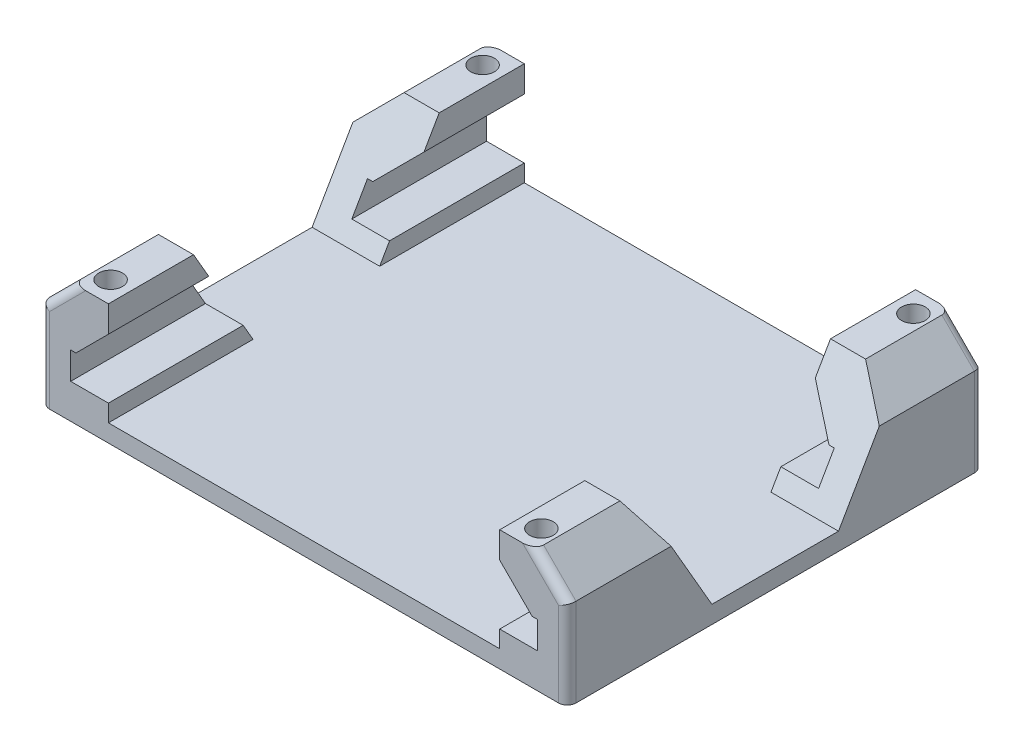
SolidWorks part; units mm, degrees
material "Delrin 2700 NC010, Low Viscosity Acetal Copolymer (SS)"
ref_plane "Front Plane" through (0, 0, 0) normal (0, 0, 1) x (1, 0, 0)
ref_plane "Top Plane" through (0, 0, 0) normal (0, 1, 0) x (1, 0, 0)
ref_plane "Right Plane" through (0, 0, 0) normal (1, 0, 0) x (0, 0, -1)
sketch "Sketch1" plane through (0, 0, 0) normal (0, 0, 1) x (1, 0, 0)
  line L0 (0, 0) -> (30, 0)
  line L1 (30, 0) -> (30, 12.7499)
  line L2 (30, 12.7499) -> (22.3001, 12.7499)
  line L3 (22.3001, 12.7499) -> (22.3001, 9.7499)
  line L4 (22.3001, 9.7499) -> (26, 6.05)
  line L5 (26, 6.05) -> (26, 4.95)
  line L6 (22.3, 1) -> (0, 1)
  line L7 (0, 1) -> (0, 0)
  line L8 (0, 0) -> (0, 12.0857) construction
  line L9 (26, 4.95) -> (22.3, 4.95)
  line L10 (22.3, 4.95) -> (22.3, 1)
  dimension "D1" = 1
  dimension "D2" = 4
  dimension "D3" = 45
  dimension "D5" = 3.95
  dimension "D6" = 1.1
  dimension "D7" = 3.7
  dimension "D8" = 3
  dimension "D9" = 0.0001
  dimension "D10" = 44.6
extrude "Boss-Extrude1" add sketch "Sketch1" against normal blind 46.4
mirror "Mirror1" about plane through (0, 1, -46.4) normal (-1, 0, 0) of bodies 101
sketch "Sketch2" plane through (0, 12.7499, 0) normal (0, 1, 0) x (1, 0, 0)
  circle A1 centre (-24.55, 2) radius 1.35 construction
  circle A2 centre (-24.55, 2) radius 1.35
  circle A13 centre (-24.55, 44.4) radius 1.35 construction
  circle A14 centre (-24.55, 44.4) radius 1.35
  circle A15 centre (24.55, 2) radius 1.35 construction
  circle A16 centre (24.55, 44.4) radius 1.35 construction
  circle A17 centre (24.55, 2) radius 1.35
  circle A18 centre (24.55, 44.4) radius 1.35
extrude "Cut-Extrude1" cut sketch "Sketch2" against normal through all
sketch "Sketch3" plane through (0, 0, 0) normal (0, 0, 1) x (1, 0, 0)
  line L0 (26.3, 12.7499) -> (30, 9.0499)
  line L1 (30, 12.7499) -> (22.3001, 12.7499) construction
  line L2 (30, 0) -> (30, 12.7499) construction
  line L3 (30, 9.0499) -> (30, 12.7499)
  line L4 (30, 12.7499) -> (26.3, 12.7499)
  line L5 (22.3001, 9.7499) -> (26, 6.05) construction
  line L7 (-30, 12.7499) -> (-30, 9.0499)
  line L8 (-30, 0) -> (-30, 12.7499) construction
  line L9 (-30, 9.0499) -> (-26.3, 12.7499)
  line L10 (-30, 12.7499) -> (-22.3001, 12.7499) construction
  line L11 (-26.3, 12.7499) -> (-30, 12.7499)
  line L12 (-22.3001, 9.7499) -> (-26, 6.05) construction
  dimension "D1" = 3.7
extrude "Cut-Extrude2" cut sketch "Sketch3" against normal through all
sketch "Sketch4" plane through (30, 0, 0) normal (1, 0, 0) x (0, 0, -1)
  line L0 (9.2, 12.7499) -> (37.2, 12.7499)
  line L1 (46.4, 12.7499) -> (0, 12.7499) construction
  line L2 (37.2, 12.7499) -> (30.4162, 1)
  line L3 (30.4162, 1) -> (15.9838, 1)
  line L4 (15.9838, 1) -> (9.2, 12.7499)
  line L5 (46.4, 1) -> (0, 1) construction
  point P9 (23.2, 12.7499)
  dimension "D1" = 28
  dimension "D2" = 60
extrude "Cut-Extrude3" cut sketch "Sketch4" against normal through all
other "Move Face1" face at (0, 6.8055, -46.4) face at (0, 6.8055, 0) offset 0.5 parameters "D1"=0.5
sketch "Sketch6" plane through (-26, 0, 0) normal (1, 0, 0) x (0, 0, -1)
  line L4 (13.7033, 4.95) -> (13.0682, 6.05)
  line L5 (13.0682, 6.05) -> (-0.5, 6.05)
  line L6 (-0.5, 6.05) -> (-0.5, 4.95)
  line L7 (-0.5, 4.95) -> (13.7033, 4.95)
  line L8 (13.7033, 4.95) -> (13.0682, 6.05)
  line L9 (13.0682, 6.05) -> (-0.5, 6.05)
  line L10 (-0.5, 6.05) -> (-0.5, 4.95)
  line L11 (-0.5, 4.95) -> (13.7033, 4.95)
  line L12 (33.3318, 6.05) -> (32.6967, 4.95)
  line L13 (32.6967, 4.95) -> (46.9, 4.95)
  line L14 (46.9, 4.95) -> (46.9, 6.05)
  line L15 (46.9, 6.05) -> (33.3318, 6.05)
  line L16 (33.3318, 6.05) -> (32.6967, 4.95)
  line L17 (32.6967, 4.95) -> (46.9, 4.95)
  line L18 (46.9, 4.95) -> (46.9, 6.05)
  line L19 (46.9, 6.05) -> (33.3318, 6.05)
  dimension "D1" = 0
  dimension "D2" = 0
extrude "Cut-Extrude5" cut sketch "Sketch6" against normal blind 0.5
sketch "Sketch7" plane through (26, 0, 0) normal (-1, 0, 0) x (0, 0, 1)
  line L4 (-13.0682, 6.05) -> (-13.7033, 4.95)
  line L5 (-13.7033, 4.95) -> (0.5, 4.95)
  line L6 (0.5, 4.95) -> (0.5, 6.05)
  line L7 (0.5, 6.05) -> (-13.0682, 6.05)
  line L8 (-13.0682, 6.05) -> (-13.7033, 4.95)
  line L9 (-13.7033, 4.95) -> (0.5, 4.95)
  line L10 (0.5, 4.95) -> (0.5, 6.05)
  line L11 (0.5, 6.05) -> (-13.0682, 6.05)
  line L12 (-32.6967, 4.95) -> (-33.3318, 6.05)
  line L13 (-33.3318, 6.05) -> (-46.9, 6.05)
  line L14 (-46.9, 6.05) -> (-46.9, 4.95)
  line L15 (-46.9, 4.95) -> (-32.6967, 4.95)
  line L16 (-32.6967, 4.95) -> (-33.3318, 6.05)
  line L17 (-33.3318, 6.05) -> (-46.9, 6.05)
  line L18 (-46.9, 6.05) -> (-46.9, 4.95)
  line L19 (-46.9, 4.95) -> (-32.6967, 4.95)
  dimension "D1" = 0
  dimension "D2" = 0
extrude "Cut-Extrude6" cut sketch "Sketch7" against normal blind 0.5
other "Move Face2" flip direction yes face at (-24.4, 4.95, -6.6016) face at (-24.4, 4.95, -39.7984) face at (24.4, 4.95, -6.6016) face at (24.4, 4.95, -39.7984) offset 2 parameters "D1"=2
other "Move Face3" face at (-24.55, 0, -43.05) offset 2 parameters "D1"=2
other "Move Face4" flip direction yes face at (-26.5, 4.5, -6.7315) face at (-26.5, 4.5, -39.6685) face at (26.5, 4.5, -6.7315) face at (26.5, 4.5, -39.6685) offset 0.1 parameters "D1"=0.1
sketch "Sketch14" plane through (0, -2, 0) normal (0, -1, 0) x (1, 0, 0)
  line L0 (-30, -46.9) -> (30, 0.5) construction
  line L1 (-15.8228, -10.7) -> (15.8228, -10.7)
  line L2 (-15.8228, -10.7) -> (-15.8228, -35.7)
  line L3 (-15.8228, -35.7) -> (15.8228, -35.7)
  line L4 (15.8228, -10.7) -> (15.8228, -35.7)
  line L5 (30, -46.9) -> (-30, 0.5) construction
  dimension "D1" = 25
extrude "Boss-Extrude4" add sketch "Sketch14" along normal blind 4
sketch "Sketch15" plane through (0, -6, 0) normal (0, -1, 0) x (1, 0, 0)
  line L0 (-15.8228, -35.7) -> (15.8228, -35.7) construction
  line L1 (-8.5, -14.7) -> (8.5, -14.7) construction
  line L2 (-8.5, -14.7) -> (-8.5, -31.7) construction
  line L3 (-8.5, -31.7) -> (8.5, -31.7) construction
  line L4 (8.5, -14.7) -> (8.5, -31.7) construction
  line L5 (-15.8228, -10.7) -> (-15.8228, -35.7) construction
  circle A0 centre (-8.5, -14.7) radius 2.1
  circle A1 centre (8.5, -14.7) radius 2.1
  circle A2 centre (8.5, -31.7) radius 2.1
  circle A3 centre (-8.5, -31.7) radius 2.1
  point P10 (0, -35.7)
  point P11 (0, -31.7)
  point P14 (-15.8228, -23.2)
  point P15 (-8.5, -23.2)
  dimension "D1" = 17
  dimension "D2" = 4.2
extrude "Cut-Extrude9" cut sketch "Sketch15" against normal through all
sketch "Sketch16" plane through (0, 1, 0) normal (0, 1, 0) x (1, 0, 0)
  circle A0 centre (-8.5, 31.7) radius 3.6
  circle A1 centre (8.5, 31.7) radius 3.6
  circle A2 centre (8.5, 14.7) radius 3.6
  circle A3 centre (-8.5, 14.7) radius 3.6
  dimension "D1" = 7.2
extrude "Cut-Extrude10" cut sketch "Sketch16" against normal blind 4.2
other "Move Face5" face at (-24.55, -2, -45.75) offset 4 parameters "D1"=4
other "Move Face6" flip direction yes face at (-24.55, -6, -45.75) offset 1 parameters "D1"=1
fillet "Fillet1" radius 1 8 edges at (30, 2.0249, -46.9) (28.15, 10.8999, -46.9) (30, 2.0249, 0.5) (28.15, 10.8999, 0.5) (-28.15, 10.8999, 0.5) (-30, 2.0249, 0.5) (-28.15, 10.8999, -46.9) (-30, 2.0249, -46.9)
other "DeleteFace1" face at (8.5, -5, -16.8) face at (8.5, -3.2, -11.1) face at (8.5, -3.2, -11.1) face at (-8.5, -5, -16.8) face at (-8.5, -3.2, -11.1) face at (-8.5, -3.2, -11.1) face at (-8.5, -5, -33.8) face at (-8.5, -3.2, -28.1) face at (-8.5, -3.2, -28.1) face at (8.5, -5, -33.8) face at (8.5, -3.2, -28.1) face at (8.5, -3.2, -28.1) and patch yes
other "DeleteFace2" face at (-25.9, 2.95, -2) face at (23.2, 2.95, -2) face at (23.2, 2.95, -44.4) face at (-25.9, 2.95, -44.4) and patch yes
other "Move Face7" flip direction yes face at (0, -5, -23.2) offset 4 parameters "D1"=4
